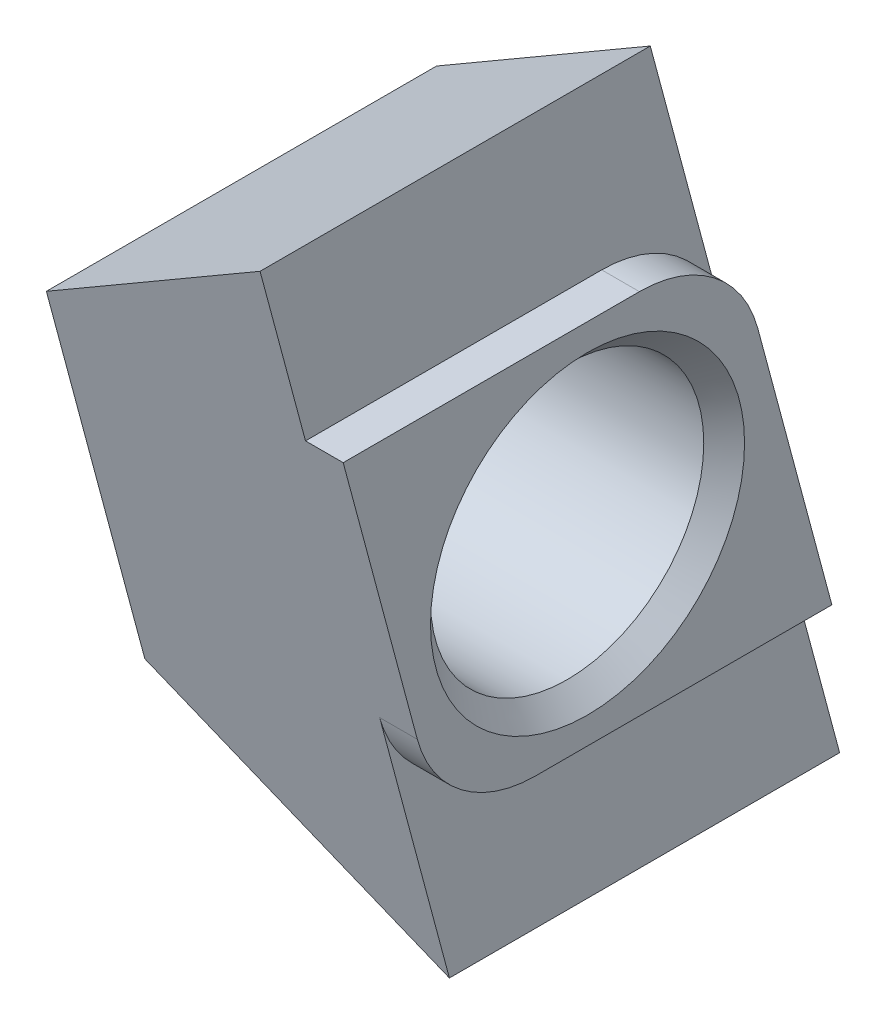
SolidWorks part; units mm, degrees
ref_plane "Piano frontale" through (0, 0, 0) normal (0, 0, 1) x (1, 0, 0)
ref_plane "Piano superiore" through (0, 0, 0) normal (0, 1, 0) x (1, 0, 0)
ref_plane "Piano destro" through (0, 0, 0) normal (1, 0, 0) x (0, 0, -1)
sketch "Sketch1" plane through (0, 0, 0) normal (1, 0, 0) x (0, 0, -1)
  line L0 (1.1011, 3.9) -> (-5.1861, 3.9)
  line L1 (-5.1861, 3.9) -> (-3.6125, -1.9729)
  line L2 (-1.1011, -3.9) -> (5.1861, -3.9)
  line L3 (5.1861, -3.9) -> (3.6125, 1.9729)
  arc A0 (-3.6125, -1.9729) -> (-1.1011, -3.9) centre (-1.1011, -1.3) ccw
  arc A1 (3.6125, 1.9729) -> (1.1011, 3.9) centre (1.1011, 1.3) ccw
extrude "Extrude1" add sketch "Sketch1" against normal blind 0.8
sketch "Sketch2" plane through (-0.8, 0, 0) normal (-1, 0, 0) x (0, 0, 1)
  line L0 (2.1315, -7.5) -> (-6.1507, -7.5)
  line L1 (-2.1315, 7.5) -> (6.1507, 7.5)
  spline S0 degree 3 poles (-2.1315, 7.5) (-3.4712, 2.5) (-4.811, -2.5) (-6.1507, -7.5) knots 0 0 0 0 1 1 1 1
  spline S1 degree 3 poles (2.1315, -7.5) (3.4712, -2.5) (4.811, 2.5) (6.1507, 7.5) knots 0 0 0 0 1 1 1 1
extrude "Extrude2" add sketch "Sketch2" along normal blind 5.5
draft "Draft1" type of draft neutral plane draft angle 33.207 faces to draft 1 face at (-3.55, 7.5, 2.0096) neutral plane through (-0.8, 0, 4.1411) neutral plane normal (1, 0, 0) reverse direction yes parameters "D1"=33.207
draft "Draft2" type of draft neutral plane draft angle 33.207 faces to draft 1 face at (-3.55, -7.5, -2.0096) neutral plane through (-0.8, 0, 4.1411) neutral plane normal (1, 0, 0) reverse direction yes parameters "D1"=33.207
hole_wizard "M5 Clearance Hole1" positions "Sketch4" profile "Sketch3" hole size "M5" standard "ANSI Metric" end condition through all
sketch "Sketch4" plane through (-6.3, 0, 0) normal (-1, 0, 0) x (0, 0, 1)
  point P0 (0, 0)
sketch "Sketch3" plane through (-6.3, 0, 0) normal (0, 1, 0) x (0, 0, 1)
  line L0 (0, 0) -> (0, 6.3)
  line L1 (0, 6.3) -> (2.9, 6.3)
  line L2 (2.9, 6.3) -> (2.9, 0)
  line L5 (2.9, 0) -> (0, 0)
  line L11 (0, -6.35) -> (0, 107.95) construction
  dimension "Thru Hole Dia." = 5.8
  dimension "Thru Hole Depth" = 6.3
chamfer "Chamfer1" distance 0.433 angle 45 2 edges at (0, 0, -2.9) (-6.3, 0, 2.9)
